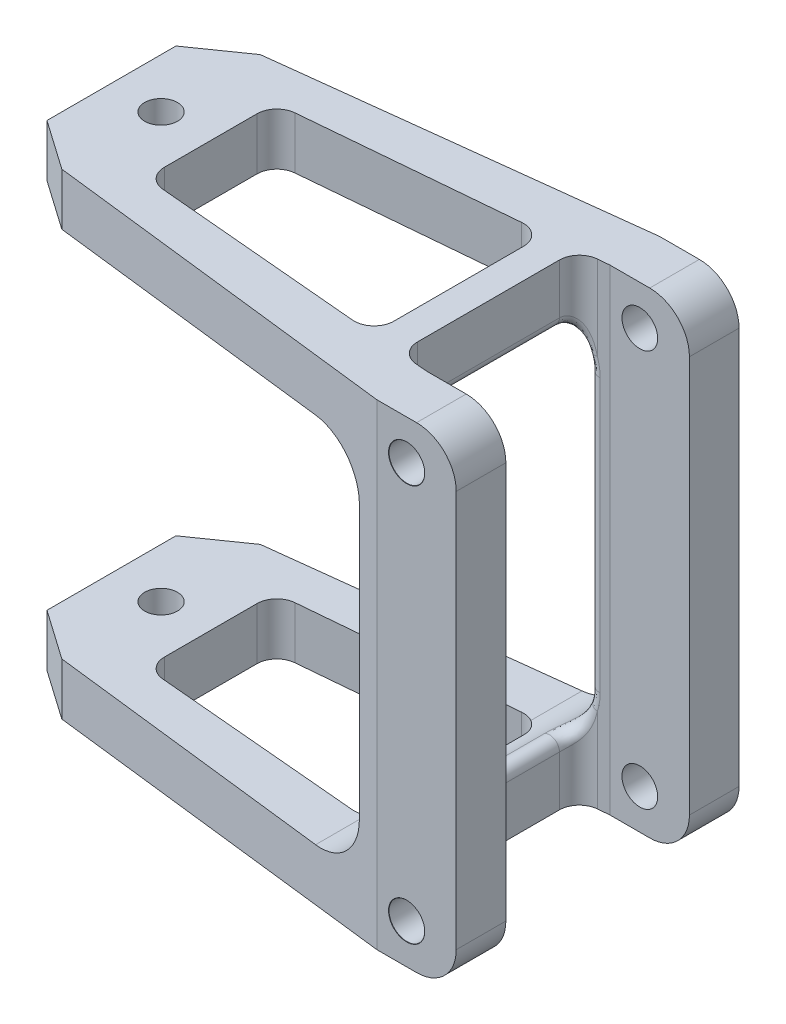
SolidWorks part; units mm, degrees
ref_plane "Front Plane" through (0, 0, 0) normal (0, 0, 1) x (1, 0, 0)
ref_plane "Top Plane" through (0, 0, 0) normal (0, 1, 0) x (1, 0, 0)
ref_plane "Right Plane" through (0, 0, 0) normal (1, 0, 0) x (0, 0, -1)
sketch "Sketch1" plane through (0, 0, 0) normal (0, 1, 0) x (1, 0, 0)
  line L0 (-20.3927, 0) -> (33.2007, 0) construction
  line L1 (0, 20.7505) -> (0, -15.7417) construction
  line L2 (0, 10) -> (-5, 6.499)
  line L3 (-5, 6.499) -> (-5, -6.499)
  line L4 (0, 10) -> (36, 14.25)
  line L5 (44, 14.25) -> (44, 9.25)
  line L6 (44, 9.25) -> (36, 9.25)
  line L7 (36, 9.25) -> (34.8232, 9.1456)
  line L8 (5, 4.6686) -> (5, -4.6686)
  line L9 (40, 19.2222) -> (40, -10.2924) construction
  line L10 (36, 14.25) -> (44, 14.25)
  line L11 (33, 7.1534) -> (33, -7.1534)
  line L12 (36, -9.25) -> (34.8232, -9.1456)
  line L13 (30, -6.5322) -> (30, 6.5322)
  line L14 (27.8232, 8.5244) -> (6.8232, 6.6608)
  line L15 (44, -9.25) -> (36, -9.25)
  line L16 (44, -14.25) -> (44, -9.25)
  line L17 (36, -14.25) -> (44, -14.25)
  line L18 (27.8232, -8.5244) -> (6.8232, -6.6608)
  line L19 (0, -10) -> (36, -14.25)
  line L20 (0, -10) -> (-5, -6.499)
  circle A0 centre (0, 0) radius 1.65
  arc A1 (34.8232, 9.1456) -> (33, 7.1534) centre (35, 7.1534) ccw
  arc A2 (27.8232, 8.5244) -> (30, 6.5322) centre (28, 6.5322) cw
  arc A3 (6.8232, 6.6608) -> (5, 4.6686) centre (7, 4.6686) ccw
  arc A4 (34.8232, -9.1456) -> (33, -7.1534) centre (35, -7.1534) cw
  arc A5 (27.8232, -8.5244) -> (30, -6.5322) centre (28, -6.5322) ccw
  arc A6 (6.8232, -6.6608) -> (5, -4.6686) centre (7, -4.6686) cw
  point P17 (36, 14.25)
  point P18 (40, 9.25)
  point P31 (30, 8.7175)
  point P34 (5, 6.499)
  point P42 (33, 0)
  point P43 (30, 0)
  point P48 (5, 0)
  point P50 (-5, 0)
  dimension "D1" = 3.3
  dimension "D12" = 2
  dimension "D2" = 18.5
  dimension "D3" = 5
  dimension "D4" = 8
  dimension "D5" = 55
  dimension "D6" = 5
  dimension "D7" = 5
  dimension "D8" = 3
  dimension "D9" = 3
  dimension "D10" = 40
  dimension "D11" = 10
extrude "Boss-Extrude1" add sketch "Sketch1" along normal blind 48
sketch "Sketch2" plane through (0, 0, 0) normal (0, 0, 1) x (1, 0, 0)
  line L0 (-5, 48) -> (-5, 0) construction
  line L1 (-5, 42.75) -> (29, 42.75)
  line L2 (-5, 42.75) -> (-5, 5.25)
  line L3 (-5, 5.25) -> (29, 5.25)
  line L4 (34, 37.75) -> (34, 10.25)
  line L7 (36, 48) -> (36, 0) construction
  line L8 (-46.4699, 24) -> (69.5076, 24) construction
  arc A0 (29, 5.25) -> (34, 10.25) centre (29, 10.25) ccw
  arc A1 (34, 37.75) -> (29, 42.75) centre (29, 37.75) ccw
  point P8 (36, 24)
  dimension "D4" = 5
  dimension "D1" = 37.5
  dimension "D3" = 2
extrude "Cut-Extrude1" cut sketch "Sketch2" against normal through all both and the other way through all
sketch "Sketch3" plane through (0, 0, 14.25) normal (0, 0, 1) x (1, 0, 0)
  line L0 (44, 48) -> (44, 0) construction
  line L3 (0, 42.75) -> (29, 42.75) construction
  line L4 (29, 5.25) -> (0, 5.25) construction
  line L5 (39, -2.0182) -> (39, 48) construction
  line L7 (-22.0716, 24) -> (69.9071, 24) construction
  circle A0 centre (39, 44) radius 1.4
  circle A1 centre (39, 4) radius 1.4
  point P3 (0, 0)
  dimension "D1" = 2.8
  dimension "D2" = 40
  dimension "D3" = 5
extrude "Cut-Extrude2" cut sketch "Sketch3" against normal through all both
hole_wizard "M3 Clearance Hole1" positions "Sketch4" profile "Sketch5" hole size "M3" standard "ANSI Metric" end condition through all
sketch "Sketch4" plane through (0, 0, 14.25) normal (0, 0, 1) x (1, 0, 0)
  point P0 (39, 44)
  point P3 (39, 4)
sketch "Sketch5" plane through (39, 44, 14.25) normal (1, 0, 0) x (0, -1, 0)
  line L0 (0, 0) -> (0, 28.5)
  line L1 (0, 28.5) -> (1.825, 28.5)
  line L2 (1.8, 28.475) -> (1.8, 0.025)
  line L3 (1.8, 0.025) -> (1.825, 0)
  line L5 (1.825, 0) -> (0, 0)
  line L6 (-1.8, 0.025) -> (-1.825, 0) construction
  line L7 (1.825, 28.5) -> (1.8, 28.475)
  line L8 (-1.825, 28.5) -> (-1.8, 28.475) construction
  line L11 (0, -6.35) -> (0, 107.95) construction
  dimension "Thru Hole Dia." = 3.6
  dimension "Thru Hole Depth" = 28.5
  dimension "Near C'Sink Dia." = 3.65
  dimension "Near C'Sink Angle" = 90
  dimension "Far C'Sink Dia." = 3.65
  dimension "Far C'Sink Angle" = 90
fillet "Fillet1" radius 4 4 edges at (44, 0, -11.75) (44, 0, 11.75) (44, 48, -11.75) (44, 48, 11.75)
fillet "Fillet5" radius 1 8 edges at (33.2542, 7.6229, -8.1292) (34, 24, -8.8854) (33.4085, 40.1091, -8.3646) (33, 40.75, 0) (33.2542, 40.3771, 8.1292) (34, 24, 8.8854) (33.4085, 7.8909, 8.3646) (33, 7.25, 0)
